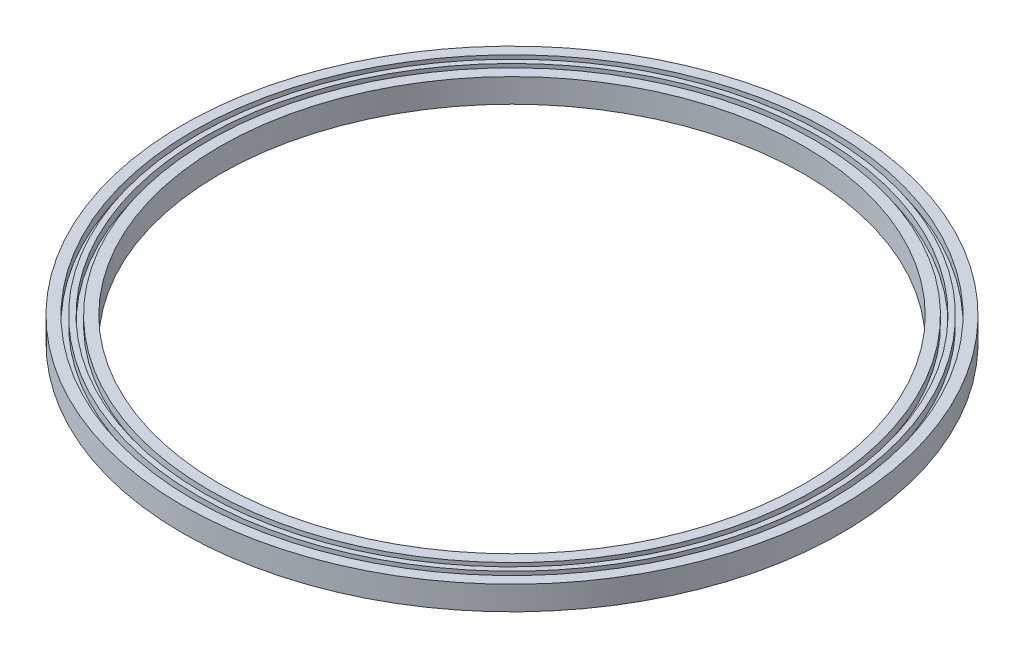
SolidWorks part; units mm, degrees
ref_plane "Front Plane" through (0, 0, 0) normal (0, 0, 1) x (1, 0, 0)
ref_plane "Top Plane" through (0, 0, 0) normal (0, 1, 0) x (1, 0, 0)
ref_plane "Right Plane" through (0, 0, 0) normal (1, 0, 0) x (0, 0, -1)
sketch "Sketch1" plane through (0, 0, 0) normal (0, 1, 0) x (1, 0, 0)
  circle A0 centre (0, 0) radius 11400
  circle A1 centre (0, 0) radius 12000
  dimension "D1" = 22800
  dimension "D2" = 24000
extrude "Boss-Extrude1" add sketch "Sketch1" along normal blind 600
sketch "Sketch2" plane through (0, 0, 0) normal (0, 1, 0) x (1, 0, 0)
  circle A0 centre (0, 0) radius 10995.1536
  circle A1 centre (0, 0) radius 11400
extrude "Boss-Extrude2" add sketch "Sketch2" along normal blind 900
sketch "Sketch3" plane through (0, 0, 0) normal (0, 1, 0) x (1, 0, 0)
  circle A0 centre (0, 0) radius 12400
  circle A1 centre (0, 0) radius 12000
extrude "Boss-Extrude3" add sketch "Sketch3" along normal blind 900
sketch "Sketch4" plane through (0, 0, 0) normal (0, -1, 0) x (1, 0, 0)
  circle A0 centre (0, 0) radius 12000
  circle A1 centre (0, 0) radius 11400
extrude "Cut-Extrude2" cut sketch "Sketch4" against normal blind 400
sketch "Sketch5" plane through (0, 600, 0) normal (0, 1, 0) x (1, 0, 0)
  circle A0 centre (0, 0) radius 12000 construction
  circle A1 centre (0, 0) radius 11400 construction
  circle A2 centre (0, 0) radius 11600.1587
  circle A3 centre (0, 0) radius 11798.4711
  dimension "D1" = 600
extrude "Boss-Extrude4" add sketch "Sketch5" along normal blind 300
